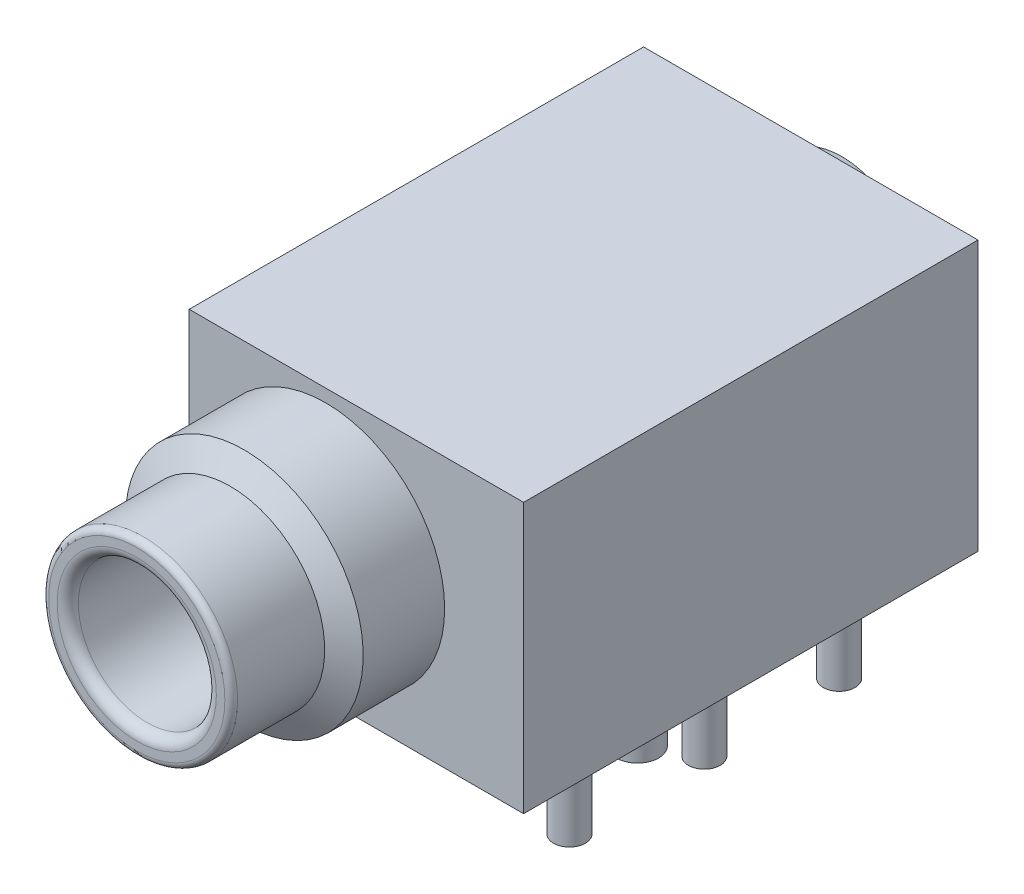
SolidWorks part; units mm, degrees
ref_plane "Front Plane" through (0, 0, 0) normal (0, 0, 1) x (1, 0, 0)
ref_plane "Top Plane" through (0, 0, 0) normal (0, 1, 0) x (1, 0, 0)
ref_plane "Right Plane" through (0, 0, 0) normal (1, 0, 0) x (0, 0, -1)
ref_plane "Plane1" through (0, 0, 0) normal (0, -1, 0) x (1, 0, 0)
sketch "Sketch1" plane through (0, 0, 0) normal (0, -1, 0) x (1, 0, 0)
  line L0 (9.32, -21.4) -> (9.32, 0)
  line L1 (9.32, 0) -> (-6.43, 0)
  line L2 (-6.43, 0) -> (-6.43, -21.4)
  line L3 (-6.43, -21.4) -> (9.32, -21.4)
extrude "Boss-Extrude1" add sketch "Sketch1" against normal blind 12.7
ref_plane "Plane2" through (0, 6.5, 0) normal (0, -1, 0) x (1, 0, 0)
sketch "Sketch2" plane through (0, 6.5, 0) normal (0, -1, 0) x (1, 0, 0)
  line L0 (4.15, -21.4) -> (0, -21.4)
  line L1 (0, -21.4) -> (0, -24.3)
  line L2 (0, -24.3) -> (3.5, -24.3)
  line L3 (3.5, -24.3) -> (4.15, -21.4)
  line L4 (0, -21.4) -> (0, -24.3) construction
revolve "Revolve1" add sketch "Sketch2" angle 360 about L4 reverse direction yes
ref_plane "Plane3" through (0, 0, -10.6) normal (0, 0, 1) x (1, 0, 0)
sketch "Sketch3" plane through (0, 0, -10.6) normal (0, 0, 1) x (1, 0, 0)
  line L0 (-3.45, 0) -> (-4.2, 0)
  line L1 (-4.2, 0) -> (-4.2, -4)
  line L2 (-4.2, -4) -> (-3.45, -4)
  line L3 (-3.45, -4) -> (-3.45, 0)
  line L4 (-4.2, 0) -> (-4.2, -4) construction
revolve "Contact Pin #1" add sketch "Sketch3" angle 360 about L4 reverse direction yes
sketch "Sketch4" plane through (0, 0, -10.6) normal (0, 0, 1) x (1, 0, 0)
  line L0 (7.98, 0) -> (7.23, 0)
  line L1 (7.23, 0) -> (7.23, -4)
  line L2 (7.23, -4) -> (7.98, -4)
  line L3 (7.98, -4) -> (7.98, 0)
  line L4 (7.23, 0) -> (7.23, -4) construction
revolve "Contact Pin #2" add sketch "Sketch4" angle 360 about L4 reverse direction yes
ref_plane "Plane4" through (0, 0, -16.95) normal (0, 0, 1) x (1, 0, 0)
sketch "Sketch5" plane through (0, 0, -16.95) normal (0, 0, 1) x (1, 0, 0)
  line L0 (-3.45, 0) -> (-4.2, 0)
  line L1 (-4.2, 0) -> (-4.2, -4)
  line L2 (-4.2, -4) -> (-3.45, -4)
  line L3 (-3.45, -4) -> (-3.45, 0)
  line L4 (-4.2, 0) -> (-4.2, -4) construction
revolve "Contact Pin #3" add sketch "Sketch5" angle 360 about L4 reverse direction yes
ref_plane "Plane5" through (0, 0, -4.25) normal (0, 0, 1) x (1, 0, 0)
sketch "Sketch6" plane through (0, 0, -4.25) normal (0, 0, 1) x (1, 0, 0)
  line L0 (-3.45, 0) -> (-4.2, 0)
  line L1 (-4.2, 0) -> (-4.2, -4)
  line L2 (-4.2, -4) -> (-3.45, -4)
  line L3 (-3.45, -4) -> (-3.45, 0)
  line L4 (-4.2, 0) -> (-4.2, -4) construction
revolve "Contact Pin #4" add sketch "Sketch6" angle 360 about L4 reverse direction yes
sketch "Sketch7" plane through (0, 0, -16.95) normal (0, 0, 1) x (1, 0, 0)
  line L0 (7.98, 0) -> (7.23, 0)
  line L1 (7.23, 0) -> (7.23, -4)
  line L2 (7.23, -4) -> (7.98, -4)
  line L3 (7.98, -4) -> (7.98, 0)
  line L4 (7.23, 0) -> (7.23, -4) construction
revolve "Contact Pin #5" add sketch "Sketch7" angle 360 about L4 reverse direction yes
sketch "Sketch8" plane through (0, 0, -4.25) normal (0, 0, 1) x (1, 0, 0)
  line L0 (7.98, 0) -> (7.23, 0)
  line L1 (7.23, 0) -> (7.23, -4)
  line L2 (7.23, -4) -> (7.98, -4)
  line L3 (7.98, -4) -> (7.98, 0)
  line L4 (7.23, 0) -> (7.23, -4) construction
revolve "Contact Pin #6" add sketch "Sketch8" angle 360 about L4 reverse direction yes
ref_plane "Plane6" through (0, 0, -13.8) normal (0, 0, 1) x (1, 0, 0)
sketch "Sketch9" plane through (0, 0, -13.8) normal (0, 0, 1) x (1, 0, 0)
  line L0 (6.6, 0) -> (5.1, 0)
  line L1 (5.1, 0) -> (5.1, -2)
  line L2 (5.1, -2) -> (6.6, -2)
  line L3 (6.6, -2) -> (6.6, 0)
  line L4 (5.1, 0) -> (5.1, -2) construction
revolve "Revolve8" add sketch "Sketch9" angle 360 about L4 reverse direction yes
ref_plane "Plane7" through (0, 0, -7.45) normal (0, 0, 1) x (1, 0, 0)
sketch "Sketch10" plane through (0, 0, -7.45) normal (0, 0, 1) x (1, 0, 0)
  line L0 (8.23, 0) -> (7.23, 0)
  line L1 (7.23, 0) -> (7.23, -2)
  line L2 (7.23, -2) -> (8.23, -2)
  line L3 (8.23, -2) -> (8.23, 0)
  line L4 (7.23, 0) -> (7.23, -2) construction
revolve "Revolve9" add sketch "Sketch10" angle 360 about L4 reverse direction yes
sketch "Sketch11" plane through (0, 0, -7.45) normal (0, 0, 1) x (1, 0, 0)
  line L0 (-3.2, 0) -> (-4.2, 0)
  line L1 (-4.2, 0) -> (-4.2, -2)
  line L2 (-4.2, -2) -> (-3.2, -2)
  line L3 (-3.2, -2) -> (-3.2, 0)
  line L4 (-4.2, 0) -> (-4.2, -2) construction
revolve "Revolve10" add sketch "Sketch11" angle 360 about L4 reverse direction yes
sketch "Sketch12" plane through (0, 6.5, 0) normal (0, -1, 0) x (1, 0, 0)
  line L0 (4.45, 8.9) -> (0, 8.9)
  line L1 (0, 8.9) -> (0, 0)
  line L2 (0, 0) -> (5.6, 0)
  line L3 (5.6, 0) -> (5.6, 3.836)
  line L4 (5.6, 3.836) -> (4.45, 4.5)
  line L5 (4.45, 4.5) -> (4.45, 8.9)
  line L6 (0, 8.9) -> (0, 0) construction
revolve "Revolve11" add sketch "Sketch12" angle 360 about L6 reverse direction yes
hole_wizard "Ø6.5 (6.5) Diameter Hole1" positions "Sketch14" profile "Sketch13" hole size "Ø6.5" standard "ANSI Metric"
sketch "Sketch14" plane through (0, 0, 8.9) normal (0, 0, 1) x (1, 0, 0)
  point P0 (0, 6.5)
sketch "Sketch13" plane through (0, 6.5, 8.9) normal (1, 0, 0) x (0, -1, 0)
  line L0 (0, 0) -> (0, 32)
  line L1 (0, 32) -> (3.25, 30.1236)
  line L2 (3.25, 30.1236) -> (3.25, 0)
  line L5 (3.25, 0) -> (0, 0)
  line L10 (0, 32) -> (-3.25, 30.1236) construction
  line L11 (0, -6.35) -> (0, 107.95) construction
  dimension "Hole Dia." = 6.5
  dimension "Hole Depth" = 30.1236
  dimension "Drill Angle" = 120
fillet "Fillet1" radius 0.3 1 edges at (-4.45, 6.5, 8.9) tangent propagation no
fillet "Fillet2" radius 0.5 1 edges at (3.25, 6.5, 8.9) tangent propagation no
